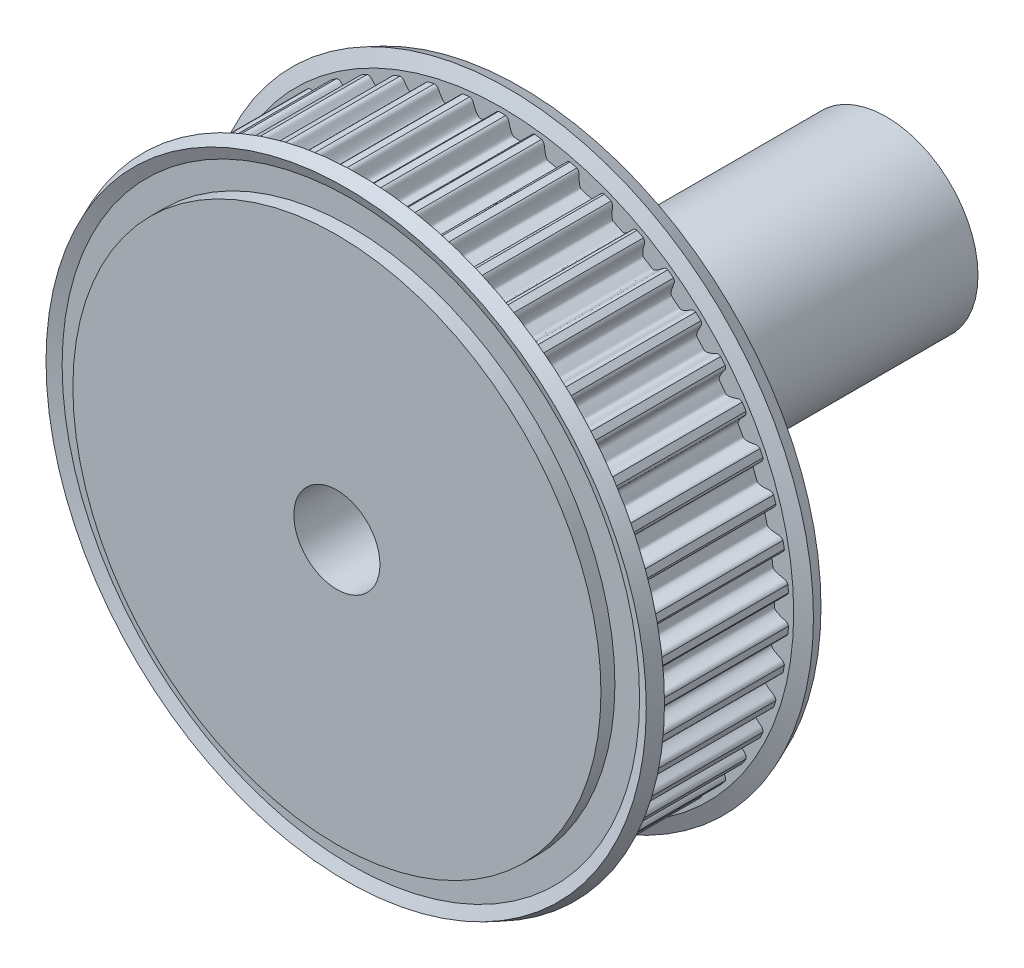
SolidWorks part; units mm, degrees
ref_plane "前视基准面" through (0, 0, 0) normal (0, 0, 1) x (1, 0, 0)
ref_plane "上视基准面" through (0, 0, 0) normal (0, 1, 0) x (1, 0, 0)
ref_plane "右视基准面" through (0, 0, 0) normal (1, 0, 0) x (0, 0, -1)
other "Configuration Table"
ref_axis "基准轴1" through (0, 0, 55) along (0, 0, -1)
sketch "SketchRevolveGearBelt01" plane through (0, 0, 0) normal (1, 0, 0) x (0, 0, -1)
  line L0 (0, 0) -> (1, 0) construction
  line L1 (5.274, 0) -> (5.274, 14.4155)
  line L2 (5.274, 14.4155) -> (4.512, 14.4155)
  line L3 (4.512, 14.4155) -> (4.512, 15.7639)
  line L4 (4.512, 15.7639) -> (4.7696, 16.3859)
  line L5 (4.7696, 16.3859) -> (4.0656, 16.6775)
  line L6 (4.0656, 16.6775) -> (3.75, 15.9155)
  line L7 (3.75, 15.9155) -> (3.75, 15.6467)
  line L8 (3.75, 15.6467) -> (-3.75, 15.6467)
  line L9 (-3.75, 15.6467) -> (-3.75, 15.9155)
  line L10 (-3.75, 15.9155) -> (-4.0656, 16.6775)
  line L11 (-4.0656, 16.6775) -> (-4.7696, 16.3859)
  line L12 (-4.7696, 16.3859) -> (-4.512, 15.7639)
  line L13 (-4.512, 15.7639) -> (-4.512, 14.4155)
  line L14 (-4.512, 14.4155) -> (-5.274, 14.4155)
  line L15 (-5.274, 14.4155) -> (-5.274, 0)
  line L16 (-5.274, 0) -> (5.274, 0)
  dimension "GearBeltFlange1OutsideLength" = 1.3484
  dimension "GearBeltFlange1X" = 0.2576
  dimension "GearBeltFlange1Y" = 0.622
  dimension "GearBeltFlangeThickness" = 0.762
  dimension "GearBeltFlangeInside" = 0.2688
  dimension "GearBeltOutsideDiameter" = 15.6467
  dimension "GearBeltFlange2X" = 0.2576
revolve "Gates_PowerGrip_GT_2mm, 6mm Belt Width" add sketch "SketchRevolveGearBelt01" angle 360 about L0
sketch "SketchToothGearBelt01" plane through (0, 0, 0) normal (0, 0, 1) x (1, 0, 0)
  arc A0 (15.6374, 0.8611) -> (15.6374, -0.8611) centre (0, 0) cw
  spline S0 degree 3 poles (15.6374, -0.8611) (15.6373, -0.8439) (15.6346, -0.8181) (15.6262, -0.7848) (15.6175, -0.7605) (15.6064, -0.7371) (15.5932, -0.7149) (15.5779, -0.6941) (15.5607, -0.6749) (15.5416, -0.6574) (15.521, -0.6419) (15.499, -0.6284) (15.4758, -0.617) (15.4348, -0.6025) (15.3828, -0.5868) (15.3217, -0.5675) (15.2692, -0.5498) (15.22, -0.5322) (15.1738, -0.5145) (15.1309, -0.4969) (15.0912, -0.4793) (15.0546, -0.4616) (15.0212, -0.444) (14.9909, -0.4264) (14.9638, -0.4087) (14.9399, -0.3911) (14.9191, -0.3735) (14.9015, -0.3558) (14.887, -0.3381) (14.8757, -0.3203) (14.8676, -0.3025) (14.8626, -0.2846) (14.8604, -0.2503) (14.8635, -0.2) (14.8637, -0.1333) (14.8645, -0.0667) (14.8646, 0) (14.8645, 0.0667) (14.8637, 0.1333) (14.8635, 0.2) (14.8604, 0.2503) (14.8626, 0.2846) (14.8676, 0.3025) (14.8757, 0.3203) (14.887, 0.3381) (14.9015, 0.3558) (14.9191, 0.3735) (14.9399, 0.3911) (14.9638, 0.4087) (14.9909, 0.4264) (15.0212, 0.444) (15.0546, 0.4616) (15.0912, 0.4793) (15.1309, 0.4969) (15.1738, 0.5145) (15.22, 0.5322) (15.2692, 0.5498) (15.3217, 0.5675) (15.3828, 0.5868) (15.4348, 0.6025) (15.4758, 0.617) (15.499, 0.6284) (15.521, 0.6419) (15.5416, 0.6574) (15.5607, 0.6749) (15.5779, 0.6941) (15.5932, 0.7149) (15.6064, 0.7371) (15.6175, 0.7605) (15.6262, 0.7848) (15.6346, 0.8181) (15.6373, 0.8439) (15.6374, 0.8611) knots 0 0 0 0 0.019649 0.029473 0.039298 0.049122 0.058947 0.068771 0.078595 0.08842 0.098244 0.108069 0.117893 0.127718 0.157726 0.179961 0.201045 0.220985 0.23979 0.257469 0.274036 0.289503 0.30389 0.317219 0.329518 0.340823 0.35118 0.36065 0.369311 0.377266 0.384647 0.39162 0.398379 0.423803 0.449202 0.474601 0.5 0.525399 0.550798 0.576197 0.601621 0.60838 0.615353 0.622734 0.630689 0.63935 0.64882 0.659177 0.670482 0.682781 0.69611 0.710497 0.725964 0.742531 0.76021 0.779015 0.798955 0.820039 0.842274 0.872282 0.882107 0.891931 0.901756 0.91158 0.921405 0.931229 0.941053 0.950878 0.960702 0.970527 0.980351 1 1 1 1
extrude "ToothExtrudeCutGearBelt01" cut sketch "SketchToothGearBelt01" against normal blind 3.75 and the other way blind 3.75
pattern_circular "Tooth Pattern, 50" count 50 every 7.2 about axis through (0, 0, 55) along (0, 0, -1) of "ToothExtrudeCutGearBelt01"
sketch "BoreRevolveSketch" plane through (0, 0, 0) normal (1, 0, 0) x (0, 0, -1)
  line L0 (0, 0) -> (1, 0) construction
  line L1 (-5.274, 0) -> (5.274, 0)
  line L2 (5.274, 0) -> (5.274, 5)
  line L3 (5.274, 5) -> (-5.274, 5)
  line L4 (-5.274, 5) -> (-5.274, 0)
  dimension "TaperSide1" = 5
  dimension "TaperSide2" = 5
revolve "BoreRevolveCut" cut sketch "BoreRevolveSketch" angle 360 about L0
sketch "AuxiliarySketchGearBelt01" plane through (0, 0, 0) normal (0, 0, 1) x (1, 0, 0)
  circle A0 centre (0, 0) radius 15.9155 construction
  dimension "PitchDiameter" = 31.831
sketch "草图5" plane through (0, 0, 5.274) normal (0, 0, 1) x (1, 0, 0)
  circle A0 centre (0, 0) radius 5
extrude "凸台-拉伸1" add sketch "草图5" against normal blind 10
sketch "草图6" plane through (0, 0, -4.726) normal (0, 0, -1) x (-1, 0, 0)
  circle A0 centre (0, 0) radius 5
  circle A1 centre (0, 0) radius 2.5
  dimension "D1" = 5
extrude "凸台-拉伸2" add sketch "草图6" along normal blind 20
sketch "草图7" plane through (0, 0, -4.726) normal (0, 0, -1) x (-1, 0, 0)
  circle A0 centre (0, 0) radius 2.5
extrude "切除-拉伸2" cut sketch "草图7" against normal blind 20
sketch "草图8" plane through (0, 0, 0) normal (0, 1, 0) x (1, 0, 0)
  line L0 (0, 24.726) -> (0, 14.726)
  line L1 (2.5, 24.726) -> (-2.5, 24.726) construction
  line L2 (0, -55) -> (0, 55) construction
  circle A0 centre (0, 14.726) radius 1.5
  dimension "D2" = 3
  dimension "D1" = 10
extrude "切除-拉伸3" cut sketch "草图8" against normal blind 20 contours A0 region at (-1.0307, 0, -13.6953)
sketch "草图9" plane through (0, 0, 5.274) normal (0, 0, 1) x (1, 0, 0)
  circle A0 centre (0, 0) radius 2.5
  circle A1 centre (0, 0) radius 2.35
  dimension "D1" = 4.7
extrude "凸台-拉伸3" add sketch "草图9" against normal blind 11
sketch "草图10" plane through (0, 0, 0) normal (1, 0, 0) x (0, 0, -1)
  line L0 (24.726, 0) -> (14.726, 0)
  line L1 (24.726, -5) -> (24.726, 5) construction
  line L2 (-55, 0) -> (55, 0) construction
  circle A0 centre (14.726, 0) radius 2
  dimension "D2" = 4
  dimension "D1" = 10
extrude "切除-拉伸4" cut sketch "草图10" against normal blind 11 contours A0 region at (0, 0, -12.7826)
sketch "草图12" plane through (0, 0, 0) normal (0, 1, 0) x (1, 0, 0)
  line L0 (0, -55) -> (0, 55) construction
  line L1 (5, 24.726) -> (-5, 24.726) construction
  circle A0 centre (0, 14.726) radius 2
  dimension "D1" = 4
  dimension "D2" = 10
extrude "切除-拉伸7" cut sketch "草图12" against normal blind 11
